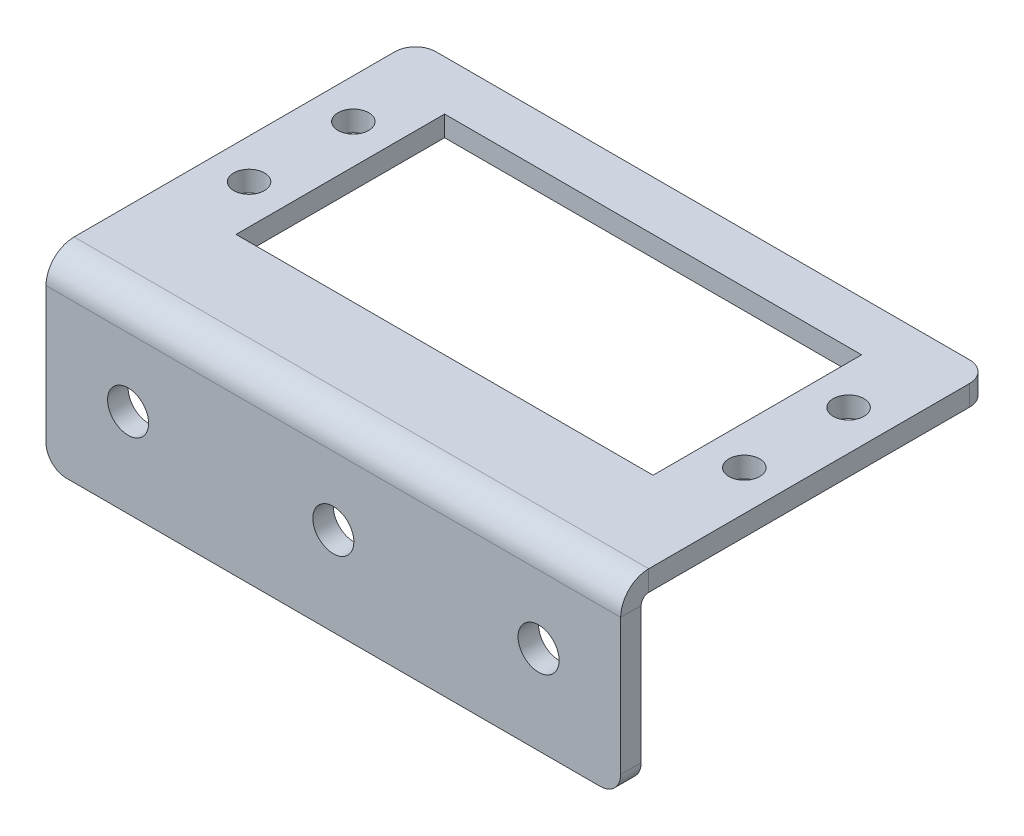
SolidWorks part; units mm, degrees
note: The reader was unsure of these and kept them because the rebuilt part matched: flange length of "Edge-Flange1".
ref_plane "Front Plane" through (0, 0, 0) normal (0, 0, 1) x (1, 0, 0)
ref_plane "Top Plane" through (0, 0, 0) normal (0, 1, 0) x (1, 0, 0)
ref_plane "Right Plane" through (0, 0, 0) normal (1, 0, 0) x (0, 0, -1)
sketch "Sketch1" plane through (0, 0, 0) normal (0, 1, 0) x (1, 0, 0)
  line L1 (-28, 17) -> (28, 17)
  line L2 (-28, 17) -> (-28, -17)
  line L3 (-28, -17) -> (28, -17)
  line L4 (28, 17) -> (28, -17)
  line L5 (-28, 17) -> (28, -17) construction
  line L6 (-28, -17) -> (28, 17) construction
  point P0 (0, 0)
base flange "Base-Flange1" sketch "Sketch1" thickness 2 reverse thickness direction no parameters "D1"=0.7366
edge flange "Edge-Flange1" sketch "Sketch8" flange angle 90 flange length 16 flange position material outside bend radius 0.7366 thickness 2 relief rectangular parameters "D6"=10
sketch "Sketch8" plane through (0, -2, 17) normal (0, 0, 1) x (-1, 0, 0)
  line L0 (28, 0) -> (-28, 0) construction
  line L1 (28, 0) -> (-28, 0)
  line L2 (-28, 0) -> (-28, 16)
  line L3 (-28, 16) -> (28, 16)
  line L4 (28, 16) -> (28, 0)
bend "EdgeBend1" bend radius 0.7366 bend angle 90 parameters "D5"=1
sketch "Sketch9" plane through (0, 0, 0) normal (0, 1, 0) x (1, 0, 0)
  line L0 (-16.6313, 12.16) -> (-24.2451, 12.16) construction
  line L2 (-20.32, 9.6265) -> (-20.32, 18.4442) construction
  line L4 (17.1242, -8.16) -> (37.1974, -8.16) construction
  line L6 (20.32, 10.3407) -> (20.32, 15.8667) construction
  line L9 (-20.32, 12.16) -> (20.32, 12.16)
  line L10 (-20.32, 12.16) -> (-20.32, -8.16)
  line L11 (-20.32, -8.16) -> (20.32, -8.16)
  line L12 (20.32, 12.16) -> (20.32, -8.16)
extrude "Cut-Extrude1" cut sketch "Sketch9" against normal through all normal cut yes
sketch "Sketch10" plane through (0, 0, 0) normal (0, 1, 0) x (1, 0, 0)
  circle A0 centre (-24.13, 7.08) radius 1.5
  circle A1 centre (-24.13, -3.08) radius 1.5
  circle A2 centre (24.13, 7.08) radius 1.5
  circle A3 centre (24.13, -3.08) radius 1.5
extrude "Cut-Extrude2" cut sketch "Sketch10" against normal through all normal cut yes
fillet "Fillet1" radius 2 4 edges at (28, -1, -17) (-28, -1, -17) (28, -18, 18) (-28, -18, 18)
sketch "Sketch11" plane through (0, 0, 17) normal (0, 0, -1) x (-1, 0, 0)
  line L0 (-30, -9.3683) -> (-13.377, -9.3683) construction
  line L2 (-28, -16) -> (-28, -2.7366) construction
  line L3 (28, -2.7366) -> (28, -16) construction
  circle A0 centre (0, -9.3683) radius 2
  circle A1 centre (-20, -9.3683) radius 2
  circle A2 centre (20, -9.3683) radius 2
  dimension "D1" = 8
  dimension "D2" = 8
extrude "Cut-Extrude3" cut sketch "Sketch11" against normal through all normal cut yes
sketch "Bend-Lines1" plane through (0, 0, 0) normal (0, 1, 0) x (1, 0, 0)
sketch "Bounding-Box1" plane through (0, 0, 0) normal (0, 1, 0) x (1, 0, 0)
sheet metal parameters "Sheet-Metal1" thickness 2 parameters "D1"=0.7366
flat pattern "Flat-Pattern1" [suppressed]
sketch "Bend-Lines2" plane through (0, 0, 0) normal (0, 1, 0) x (1, 0, 0)
sketch "Bounding-Box2" [suppressed] plane through (0, 0, 0) normal (0, 1, 0) x (1, 0, 0)
sheet metal parameters "Sheet-Metal2" thickness 2 parameters "D1"=0.7366
flat pattern "Flat-Pattern1" [suppressed]
sketch "Bend-Lines2" plane through (0, 0, 0) normal (0, 1, 0) x (1, 0, 0)
sketch "Bounding-Box2" [suppressed] plane through (0, 0, 0) normal (0, 1, 0) x (1, 0, 0)
bend of the flat pattern "Flatten-<EdgeBend1>1"
sheet metal parameters "Sheet-Metal3" thickness 2 parameters "D1"=0.7366
flat pattern "Flat-Pattern1" [suppressed]
sketch "Bend-Lines2" plane through (0, 0, 0) normal (0, 1, 0) x (1, 0, 0)
sketch "Bounding-Box2" [suppressed] plane through (0, 0, 0) normal (0, 1, 0) x (1, 0, 0)
bend of the flat pattern "Flatten-<EdgeBend1>1"
sheet metal parameters "Sheet-Metal4" thickness 2 parameters "D1"=0.7366
flat pattern "Flat-Pattern1" [suppressed]
sketch "Bend-Lines2" plane through (0, 0, 0) normal (0, 1, 0) x (1, 0, 0)
sketch "Bounding-Box2" [suppressed] plane through (0, 0, 0) normal (0, 1, 0) x (1, 0, 0)
bend of the flat pattern "Flatten-<EdgeBend1>1"
sheet metal parameters "Sheet-Metal5" thickness 2 parameters "D1"=0.7366
flat pattern "Flat-Pattern1" [suppressed]
sketch "Bend-Lines2" plane through (0, 0, 0) normal (0, 1, 0) x (1, 0, 0)
sketch "Bounding-Box2" [suppressed] plane through (0, 0, 0) normal (0, 1, 0) x (1, 0, 0)
bend of the flat pattern "Flatten-<EdgeBend1>1"
